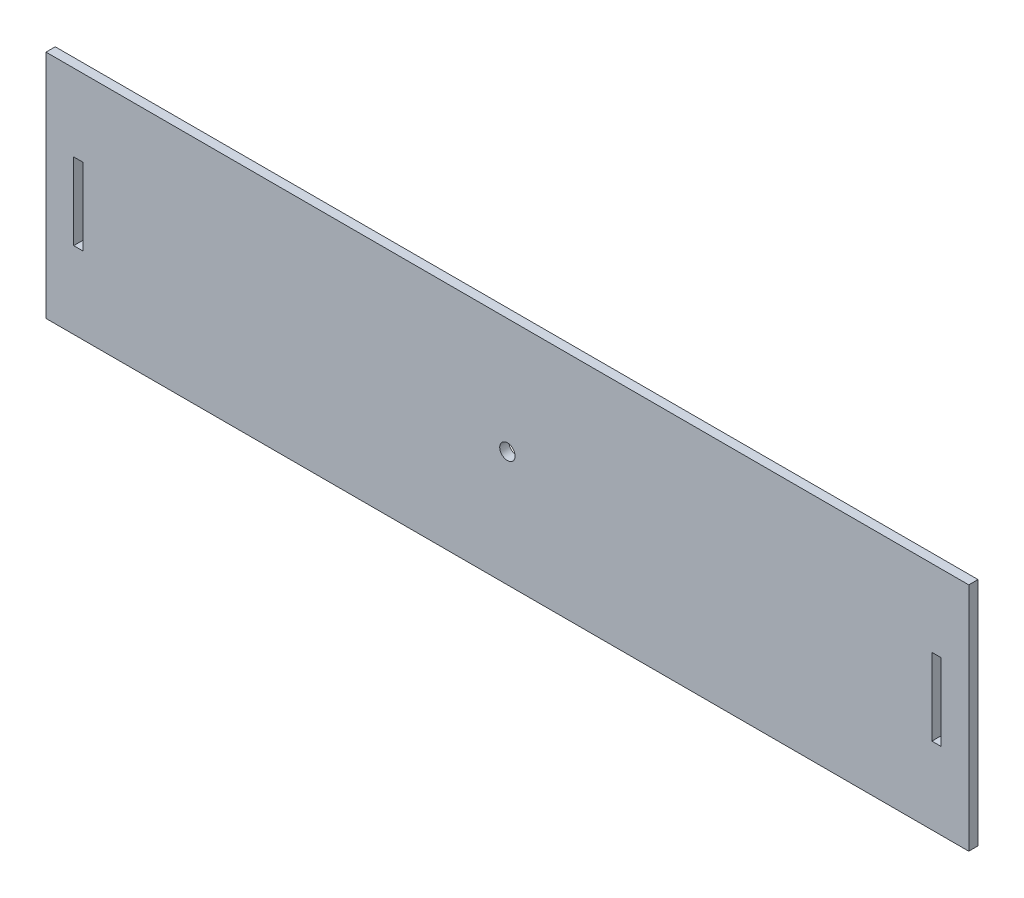
SolidWorks part; units mm, degrees
material "Maple"
ref_plane "Front Plane" through (0, 0, 0) normal (0, 0, 1) x (1, 0, 0)
ref_plane "Top Plane" through (0, 0, 0) normal (0, 1, 0) x (1, 0, 0)
ref_plane "Right Plane" through (0, 0, 0) normal (1, 0, 0) x (0, 0, -1)
sketch "Sketch1" plane through (0, 0, 0) normal (0, 0, 1) x (1, 0, 0)
  line L0 (300, 0) -> (300, -150) construction
  line L1 (0, 0) -> (600, 0)
  line L2 (0, 0) -> (0, -150)
  line L3 (0, -150) -> (257, -150)
  line L4 (600, 0) -> (600, -150)
  line L5 (600, -75) -> (0, -75) construction
  line L6 (307, -150) -> (600, -150)
  line L11 (582, -100) -> (576, -100)
  line L12 (18, -50) -> (24, -50)
  line L13 (18, -50) -> (18, -100)
  line L14 (18, -100) -> (24, -100)
  line L15 (24, -50) -> (24, -100)
  line L16 (18, -50) -> (24, -100) construction
  line L17 (18, -100) -> (24, -50) construction
  line L18 (576, -50) -> (576, -100)
  line L19 (582, -50) -> (576, -50)
  line L20 (582, -50) -> (582, -100)
  line L21 (307, -150) -> (257, -150)
  circle A0 centre (300, -75) radius 5
  point P6 (300, -34.6496)
  point P10 (21, -75)
  point P22 (300, -63)
  point P23 (300, -26)
  dimension "D3" = 10
  dimension "D1" = 600
  dimension "D2" = 150
  dimension "D4" = 6
  dimension "D5" = 50
  dimension "D6" = 18
  dimension "D7" = 6
  dimension "D8" = 6
extrude "Boss-Extrude1" add sketch "Sketch1" along normal blind 6
